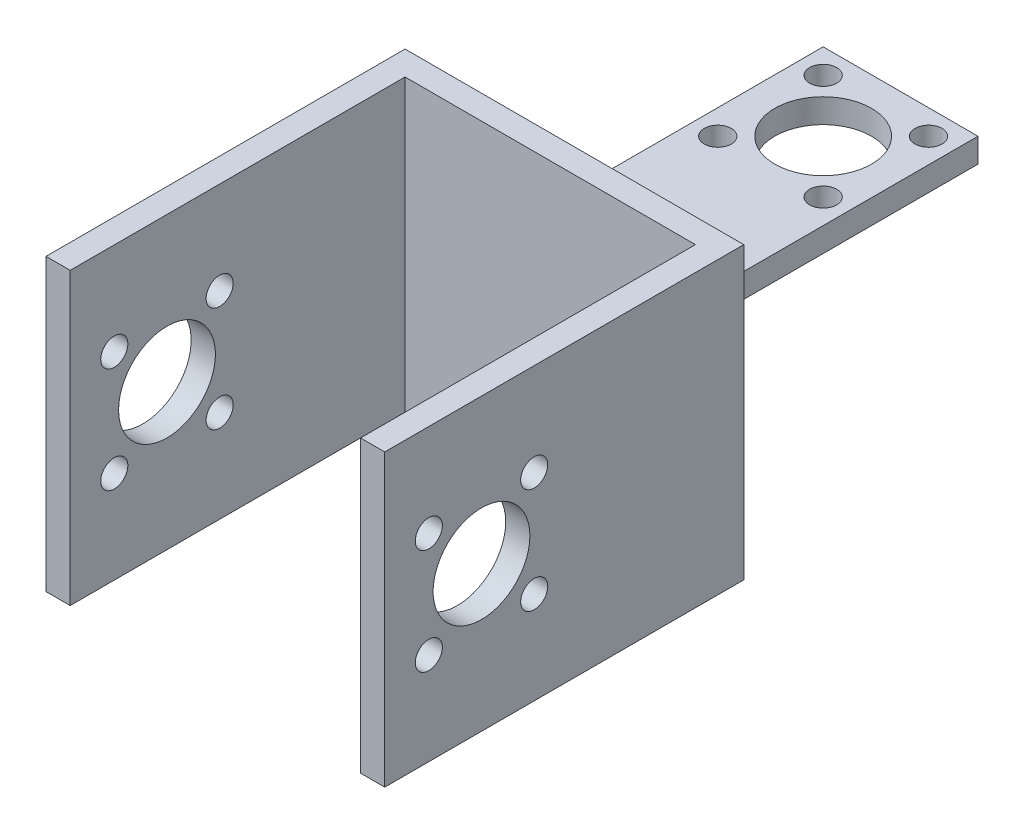
SolidWorks part; units mm, degrees
ref_plane "Front Plane" through (0, 0, 0) normal (0, 0, 1) x (1, 0, 0)
ref_plane "Top Plane" through (0, 0, 0) normal (0, 1, 0) x (1, 0, 0)
ref_plane "Right Plane" through (0, 0, 0) normal (1, 0, 0) x (0, 0, -1)
sketch "Sketch1" plane through (0, 0, 0) normal (0, 1, 0) x (1, 0, 0)
  line L0 (0, 0) -> (-20.32, 0)
  line L1 (-20.32, 0) -> (-20.32, -43.561)
  line L2 (0, 0) -> (0, -43.561)
  line L3 (-20.32, -43.561) -> (-31.623, -43.561)
  line L4 (-31.623, -43.561) -> (-31.623, -90.678)
  line L5 (-31.623, -90.678) -> (-28.448, -90.678)
  line L6 (-28.448, -90.678) -> (-28.448, -46.736)
  line L7 (-28.448, -46.736) -> (9.652, -46.736)
  line L8 (9.652, -46.736) -> (9.652, -90.678)
  line L9 (0, -43.561) -> (12.827, -43.561)
  line L10 (9.652, -90.678) -> (12.827, -90.678)
  line L11 (12.827, -43.561) -> (12.827, -90.678)
  dimension "D1" = 20.32
  dimension "D2" = 46.736
  dimension "D3" = 43.561
  dimension "D4" = 38.1
  dimension "D5" = 3.175
  dimension "D6" = 3.175
  dimension "D8" = 90.678
  dimension "D9" = 90.678
  dimension "D10" = 43.561
extrude "Boss-Extrude1" add sketch "Sketch1" along normal mid plane 38.1
sketch "Sketch3" plane through (0, -19.05, 0) normal (0, -1, 0) x (1, 0, 0)
  line L0 (0, 43.561) -> (-20.32, 43.561)
  line L1 (-20.32, 43.561) -> (-20.32, 0)
  line L2 (-20.32, 0) -> (0, 0)
  line L3 (0, 0) -> (0, 43.561)
extrude "Cut-Extrude1" cut sketch "Sketch3" against normal blind 19.05
sketch "Sketch4" plane through (0, 19.05, 0) normal (0, 1, 0) x (1, 0, 0)
  line L0 (-20.32, -43.561) -> (0, -43.561)
  line L1 (0, -43.561) -> (0, 0)
  line L2 (0, 0) -> (-20.32, 0)
  line L3 (-20.32, 0) -> (-20.32, -43.561)
extrude "Cut-Extrude2" cut sketch "Sketch4" against normal blind 15.875
sketch "Sketch6" plane through (0, 3.175, 0) normal (0, 1, 0) x (1, 0, 0)
  line L0 (-10.16, 0) -> (-10.16, -20.32) construction
  line L1 (0, 0) -> (-20.32, 0) construction
  line L2 (-10.16, -10.16) -> (-17.0748, -17.0748) construction
  line L3 (-10.16, -10.16) -> (-17.0748, -3.2452) construction
  line L4 (-10.16, -10.16) -> (-3.2452, -3.2452) construction
  line L5 (-10.16, -10.16) -> (-3.2452, -17.0748) construction
  circle A0 centre (-10.16, -10.16) radius 6.35
  circle A1 centre (-17.0748, -17.0748) radius 1.778
  circle A2 centre (-17.0748, -3.2452) radius 1.778
  circle A3 centre (-3.2452, -3.2452) radius 1.778
  circle A4 centre (-3.2452, -17.0748) radius 1.778
extrude "Cut-Extrude3" cut sketch "Sketch6" against normal up to next
sketch "Sketch9" plane through (12.827, 0, 0) normal (1, 0, 0) x (0, 0, -1)
  line L0 (-90.678, 0) -> (-65.278, 0) construction
  line L1 (-90.678, 19.05) -> (-90.678, -19.05) construction
  line L2 (-77.978, 0) -> (-84.8928, 6.9148) construction
  line L3 (-77.978, 0) -> (-84.8928, -6.9148) construction
  line L4 (-77.978, 0) -> (-71.0632, -6.9148) construction
  line L5 (-77.978, 0) -> (-71.0632, 6.9148) construction
  circle A0 centre (-77.978, 0) radius 6.35
  circle A1 centre (-84.8928, 6.9148) radius 1.778
  circle A2 centre (-71.0632, 6.9148) radius 1.778
  circle A3 centre (-71.0632, -6.9148) radius 1.778
  circle A4 centre (-84.8928, -6.9148) radius 1.778
extrude "Cut-Extrude6" cut sketch "Sketch9" against normal up to next
sketch "Sketch10" plane through (-31.623, 0, 0) normal (-1, 0, 0) x (0, 0, 1)
  line L0 (90.678, 0) -> (65.278, 0) construction
  line L1 (90.678, 19.05) -> (90.678, -19.05) construction
  line L2 (77.978, 0) -> (84.8928, 6.9148) construction
  line L3 (77.978, 0) -> (84.8928, -6.9148) construction
  line L4 (77.978, 0) -> (71.0632, -6.9148) construction
  line L5 (77.978, 0) -> (71.0632, 6.9148) construction
  circle A0 centre (77.978, 0) radius 6.35
  circle A1 centre (71.0632, 6.9148) radius 1.778
  circle A2 centre (84.8928, 6.9148) radius 1.778
  circle A3 centre (84.8928, -6.9148) radius 1.778
  circle A4 centre (71.0632, -6.9148) radius 1.778
extrude "Cut-Extrude7" cut sketch "Sketch10" against normal up to next
